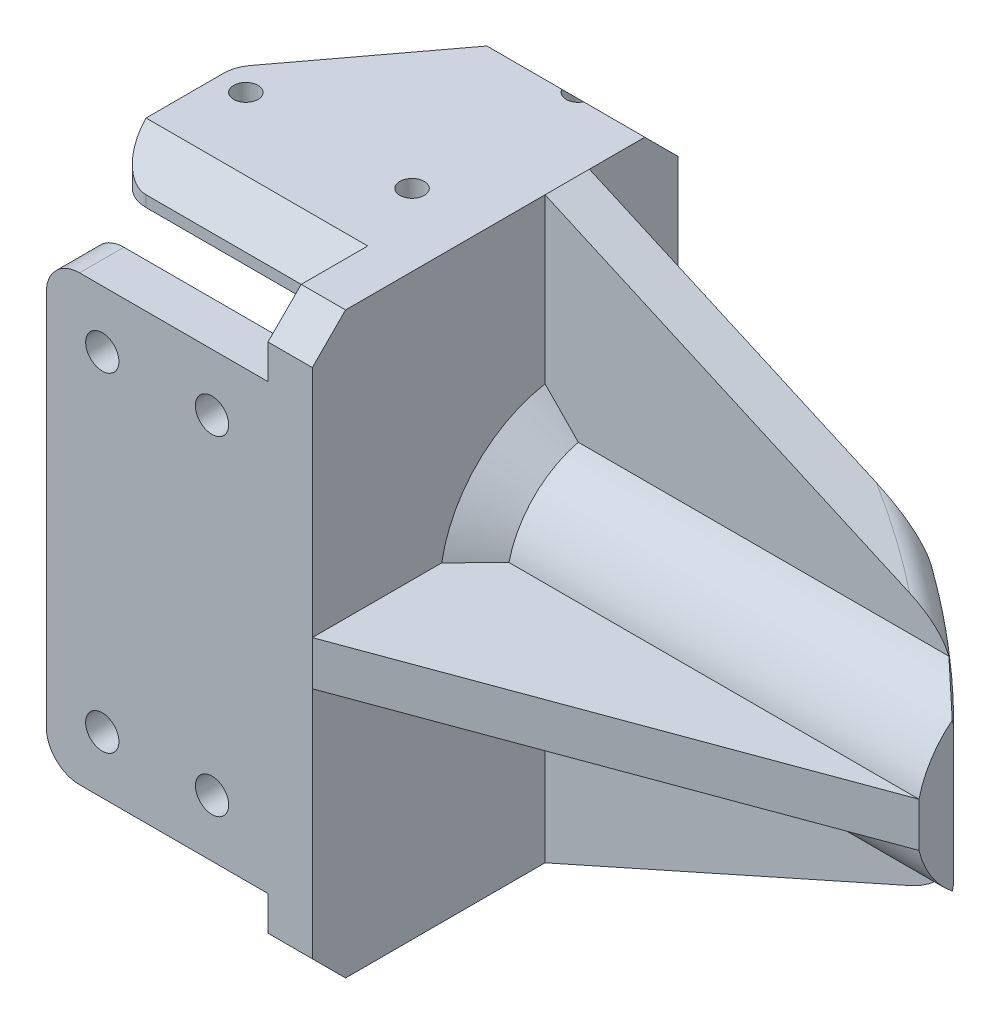
SolidWorks part; units mm, degrees
ref_plane "Спереди" through (0, 0, 0) normal (0, 0, 1) x (1, 0, 0)
ref_plane "Сверху" through (0, 0, 0) normal (0, 1, 0) x (1, 0, 0)
ref_plane "Справа" through (0, 0, 0) normal (1, 0, 0) x (0, 0, -1)
sketch "Sketch1" plane through (0, 0, 0) normal (0, 1, 0) x (1, 0, 0)
  line L5 (-12, -10) -> (12, -10)
  line L6 (-12, -10) -> (-12, 10)
  line L7 (-12, 10) -> (12, 10)
  line L8 (12, -10) -> (12, 10)
  line L9 (-12, -10) -> (12, 10) construction
  line L10 (-12, 10) -> (12, -10) construction
  point P0 (0, 0)
  dimension "D1" = 20
  dimension "D2" = 24
extrude "Boss-Extrude1" add sketch "Sketch1" along normal blind 52.2 contours L5 | L5 region at (0, 0, 0)
sketch "Sketch3" plane through (0, 0, 10) normal (0, 0, 1) x (1, 0, 0)
  line L0 (-12, 52.2) -> (-12, 0) construction
  line L1 (-12, 4) -> (8, 4)
  line L2 (-12, 4) -> (-12, 48.2)
  line L3 (-12, 48.2) -> (8, 48.2)
  line L4 (8, 4) -> (8, 48.2)
  line L5 (-12, 0) -> (12, 0) construction
  line L6 (12, 52.2) -> (12, 0) construction
  line L7 (-12, 52.2) -> (12, 52.2) construction
  dimension "D1" = 4
  dimension "D2" = 4
  dimension "D3" = 4
extrude "Cut-Extrude2" cut sketch "Sketch3" against normal blind 52.2
sketch "Sketch4" plane through (0, 52.2, 0) normal (0, 1, 0) x (1, 0, 0)
  line L0 (-12, 0) -> (-2, 0) construction
  line L1 (-12, -10) -> (-12, 10) construction
  line L2 (-2, 0) -> (-2, 5.3635) construction
  circle A0 centre (-9.5, -7.5) radius 1.1
  circle A1 centre (-9.5, 7.5) radius 1.1
  circle A2 centre (5.5, 7.5) radius 1.1
  circle A3 centre (5.5, -7.5) radius 1.1
  dimension "D1" = 2.2
  dimension "D3" = 15
  dimension "D4" = 15
  dimension "D2" = 10
extrude "Cut-Extrude3" cut sketch "Sketch4" against normal through all
sketch "Sketch5" plane through (0, 0, 0) normal (0, -1, 0) x (1, 0, 0)
  line L0 (-12, -10) -> (0, -10)
  line L1 (-12, -10) -> (12, -10) construction
  line L2 (-12, -10) -> (-12, 6)
  line L3 (-12, 10) -> (-12, -10) construction
  line L4 (-12, 6) -> (0, -10)
  dimension "D1" = 12
  dimension "D2" = 16
extrude "Cut-Extrude4" cut sketch "Sketch5" against normal through all
sketch "Sketch6" plane through (0, 0, 0) normal (0, -1, 0) x (1, 0, 0)
  line L5 (-12, 10) -> (-12, 6)
  line L6 (-12, 6) -> (0, -10)
  line L7 (0, -10) -> (12, -10)
  line L8 (12, -10) -> (12, 10)
  line L9 (12, 10) -> (-12, 10)
  line L10 (-12, 10) -> (-12, 6)
  line L11 (-12, 6) -> (0, -10)
  line L12 (0, -10) -> (12, -10)
  line L13 (12, -10) -> (12, 10)
  line L14 (12, 10) -> (-12, 10)
  dimension "D1" = 0
extrude "Boss-Extrude2" add sketch "Sketch6" against normal blind 4
sketch "Sketch7" plane through (0, 0, 0) normal (0, -1, 0) x (1, 0, 0)
  line L0 (-12, 6) -> (-12, -22.8253) construction
  line L2 (-2, 0) -> (-12, 0) construction
  circle A0 centre (-2, 0) radius 7 construction
  circle A1 centre (5, 0) radius 1.1
  circle A2 centre (-2, -7) radius 1.1
  circle A3 centre (-9, 0) radius 1.1
  circle A4 centre (-2, 7) radius 1.1
  point P3 (0, 0)
  point P4 (-2, 0)
  point P17 (-2, 0)
  dimension "D2" = 14
  dimension "D3" = 2.2
  dimension "D1" = 10
  dimension "D4" = 4
extrude "Cut-Extrude5" cut sketch "Sketch7" against normal blind 4
sketch "Sketch8" plane through (0, 0, 10) normal (0, 0, 1) x (1, 0, 0)
  line L8 (8, 4) -> (-12, 4)
  line L9 (-12, 4) -> (-12, 0)
  line L10 (-12, 0) -> (12, 0)
  line L11 (12, 0) -> (12, 52.2)
  line L12 (12, 52.2) -> (-12, 52.2)
  line L13 (-12, 52.2) -> (-12, 48.2)
  line L14 (-12, 48.2) -> (8, 48.2)
  line L15 (8, 48.2) -> (8, 4)
  line L16 (8, 4) -> (-12, 4)
  line L18 (-12, 0) -> (12, 0)
  line L19 (12, 0) -> (12, 52.2)
  line L20 (12, 52.2) -> (-12, 52.2)
  line L21 (-12, 52.2) -> (-12, 48.2)
  line L22 (-12, 48.2) -> (8, 48.2)
  line L23 (8, 48.2) -> (8, 4)
  line L24 (-12, 4) -> (-12, 0)
  dimension "D1" = 0
extrude "Boss-Extrude3" add sketch "Sketch8" along normal blind 7
sketch "Sketch9" plane through (0, 0, 17) normal (0, 0, 1) x (1, 0, 0)
  line L0 (-12, 0) -> (12, 0) construction
  line L1 (12, 52.2) -> (8, 52.2)
  line L2 (12, 52.2) -> (12, 0)
  line L3 (12, 0) -> (8, 0)
  line L4 (8, 52.2) -> (8, 0)
  dimension "D1" = 4
extrude "Boss-Extrude4" add sketch "Sketch9" along normal blind 6
sketch "Sketch12" plane through (8, 0, 0) normal (-1, 0, 0) x (0, 0, 1)
  line L0 (23, 52.2) -> (23, 0) construction
  line L1 (27, 46.1) -> (19, 46.1)
  line L2 (27, 46.1) -> (27, 6.1)
  line L3 (27, 6.1) -> (19, 6.1)
  line L4 (19, 46.1) -> (19, 6.1)
  line L5 (27, 46.1) -> (19, 6.1) construction
  line L6 (27, 6.1) -> (19, 46.1) construction
  point P0 (23, 26.1)
  line M5 (23, 0) -> (23, 52.2)
  dimension "D1" = 40
  dimension "D2" = 8
extrude "Boss-Extrude5" add sketch "Sketch12" along normal blind 20 contours L1 L4 L3 M5 region at (8, 26.1, 21)
sketch "Sketch13" plane through (0, 0, 23) normal (0, 0, 1) x (1, 0, 0)
  line L0 (8, 46.1) -> (-12, 6.1) construction
  line L1 (2.7339, 26.1) -> (-2.0002, 26.0996) construction
  line L2 (-2.0002, 26.0996) -> (-2.0002, 35.2652) construction
  circle A0 centre (2.9498, 40.95) radius 1.5
  circle A1 centre (2.9523, 11.25) radius 1.5
  circle A2 centre (-6.9527, 11.25) radius 1.5
  circle A3 centre (-6.9502, 40.95) radius 1.5
  dimension "D1" = 3
  dimension "D2" = 9.9
  dimension "D3" = 29.7
extrude "Cut-Extrude6" cut sketch "Sketch13" against normal blind 20
sketch "Sketch14" plane through (12, 0, 0) normal (1, 0, 0) x (0, 0, -1)
  line L0 (0, 52.2) -> (0, 0) construction
  line L1 (-23, 52.2) -> (10, 52.2) construction
  line L2 (-23, 0) -> (10, 0) construction
  line L3 (10, 52.2) -> (10, 0) construction
  circle A1 centre (0, 26.1) radius 4.5
  circle A2 centre (0, 26.1) radius 8.5
  point P12 (0, 26.4649)
  dimension "D1" = 10
  dimension "D2" = 9
  dimension "D3" = 4
extrude "Boss-Extrude6" add sketch "Sketch14" along normal blind 40
sketch "Sketch16" plane through (12, 0, 0) normal (1, 0, 0) x (0, 0, -1)
  line L0 (-23, 0) -> (10, 0) construction
  line L1 (2, 52.2) -> (-2, 52.2)
  line L2 (2, 52.2) -> (2, 0)
  line L3 (2, 0) -> (-2, 0)
  line L4 (-2, 52.2) -> (-2, 0)
  line L5 (2, 52.2) -> (-2, 0) construction
  line L6 (2, 0) -> (-2, 52.2) construction
  line L7 (0, 26.1) -> (-23, 26.1) construction
  line L8 (-23, 0) -> (-23, 52.2) construction
  line L10 (0, 24.1) -> (-23, 24.1)
  line L11 (0, 24.1) -> (0, 28.1)
  line L12 (0, 28.1) -> (-23, 28.1)
  line L13 (-23, 24.1) -> (-23, 28.1)
  line L14 (0, 24.1) -> (-23, 28.1) construction
  line L15 (0, 28.1) -> (-23, 24.1) construction
  point P0 (0, 26.1)
  point P12 (-11.5, 26.1)
  circle M5 centre (0, 26.1) radius 8.5
  line M6 (-23, 52.2) -> (-23, 0)
  line M8 (-23, 0) -> (10, 0)
  line M10 (10, 52.2) -> (-23, 52.2)
  dimension "D1" = 4
  dimension "D2" = 4
  dimension "D3" = 23
extrude "Boss-Extrude7" add sketch "Sketch16" along normal blind 40 contours L4 L2 M10 M5 | L4 L2 M5 M8 | L12 L10 M5 M6 region at (12, 43.3603, 0) region at (12, 8.8397, 0) region at (12, 26.1, 15.7103)
sketch "Sketch17" plane through (0, 0, 2) normal (0, 0, 1) x (1, 0, 0)
  line L0 (52, 52.2) -> (12, 52.2)
  line L1 (12, 52.2) -> (12, 34.3614) construction
  line L2 (52, 52.2) -> (12, 52.2) construction
  line L3 (12, 52.2) -> (52, 34.3614)
  line L4 (52, 34.3614) -> (52, 52.2)
  line L5 (52, 26.1) -> (28.3958, 26.1) construction
  line L7 (12, 0) -> (52, 17.8386)
  line L8 (52, 0) -> (12, 0)
  line L9 (52, 17.8386) -> (52, 0)
  line L10 (52, 17.8386) -> (52, 34.3614) construction
  point P16 (0, 0)
  point P17 (52, 26.1)
extrude "Cut-Extrude7" cut sketch "Sketch17" against normal blind 40
sketch "Sketch18" plane through (0, 24.1, 0) normal (0, -1, 0) x (1, 0, 0)
  line L0 (52, 8.2614) -> (12, 23)
  line L1 (12, 23) -> (52, 23)
  line L2 (52, 23) -> (52, 8.2614)
extrude "Cut-Extrude8" cut sketch "Sketch18" against normal blind 40
chamfer "Chamfer1" distance 3 angle 45 2 edges at (12, 32.1104, 6.0104) (12, 20.0896, 6.0104)
sketch "Sketch19" plane through (52, 0, 0) normal (1, 0, 0) x (0, 0, -1)
  line L0 (-8.2614, 26.1) -> (8.5, 26.1) construction
  line L1 (-8.2614, 28.1) -> (-8.2614, 24.1) construction
  arc A0 (2, 17.8386) -> (2, 34.3614) centre (0, 26.1) ccw construction
ref_plane "Plane1" through (0, 26.1, 0) normal (0, -1, 0) x (0, 0, -1)
sketch "Sketch20" plane through (0, 26.1, 0) normal (0, -1, 0) x (0, 0, -1)
  line L0 (-2, 52) -> (-8.2614, 52) construction
  line L1 (-5.1307, 52) -> (8.5, 52)
  line L2 (8.5, 52) -> (8.5, 24.9166)
  arc A0 (-5.1307, 52) -> (8.5, 12) centre (-38.0542, 18.4583) cw
  point P9 (8, 52)
  dimension "D1" = 47
extrude "Cut-Extrude9" cut sketch "Sketch20" against normal through all both and the other way through all contours L1 A0 L2 region at (44.525, 26.1, -4.4811)
fillet "Fillet1" radius 3 2 edges at (45.9019, 37.0809, -0.1015) (45.9019, 15.1191, -0.1015)
sketch "Sketch21" plane through (0, 0, -10) normal (0, 0, -1) x (-1, 0, 0)
  line L0 (-12, 34.3614) -> (-12, 17.8386) construction
  line L1 (-14, 30.1) -> (-10, 30.1)
  line L2 (-14, 30.1) -> (-14, 22.1)
  line L3 (-14, 22.1) -> (-10, 22.1)
  line L4 (-10, 30.1) -> (-10, 22.1)
  line L5 (-14, 30.1) -> (-10, 22.1) construction
  line L6 (-14, 22.1) -> (-10, 30.1) construction
  point P0 (-12, 26.1)
  dimension "D1" = 8
  dimension "D2" = 4
extrude "Cut-Extrude11" cut sketch "Sketch21" against normal blind 10
chamfer "Chamfer3" distance 3 angle 45 6 edges at (-2, 0, 17) (-2, 52.2, 17) (10, 52.2, 23) (6, 52.2, -10) (10, 0, 23) (6, 0, -10)
fillet "Fillet2" radius 3 8 edges at (0, 3.5, -10) (-12, 2, 6) (-12, 50.2, 6) (0, 48.7, -10) (-12, 48.7, 17) (-12, 46.1, 21) (-12, 3.5, 17) (-12, 6.1, 21)
